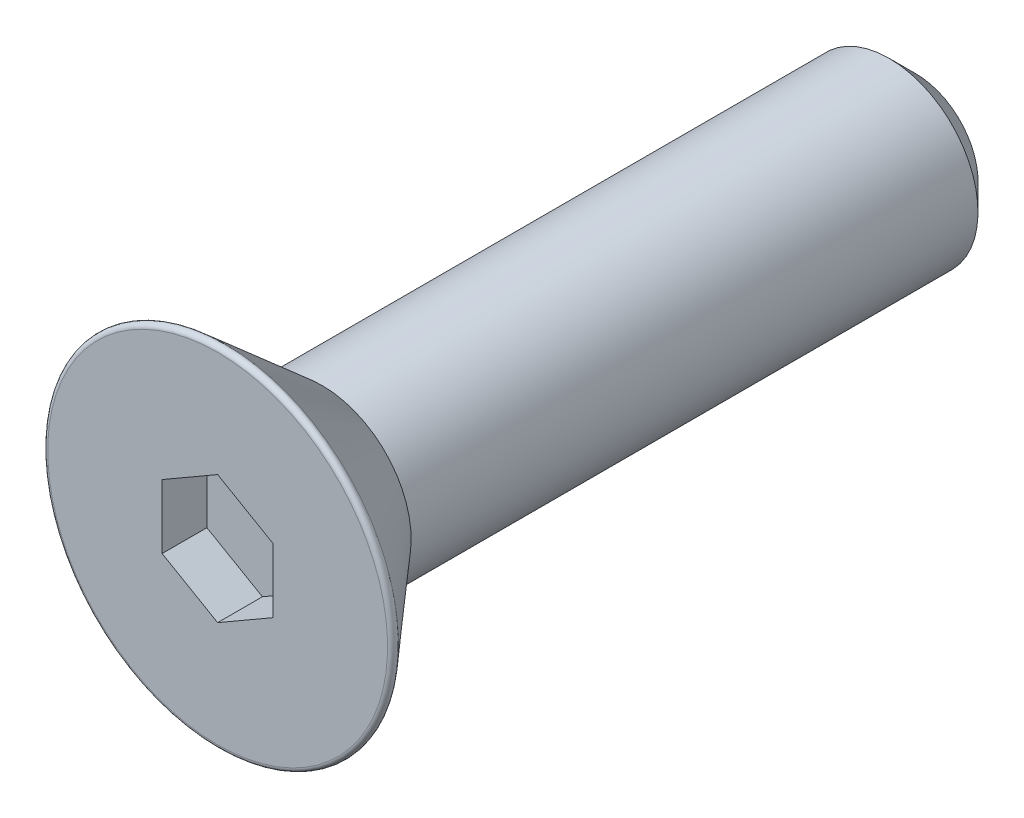
SolidWorks part; units mm, degrees
material "Alloy Steel"
ref_plane "Front Plane" through (0, 0, 0) normal (0, 0, 1) x (1, 0, 0)
ref_plane "Top Plane" through (0, 0, 0) normal (0, 1, 0) x (1, 0, 0)
ref_plane "Right Plane" through (0, 0, 0) normal (1, 0, 0) x (0, 0, -1)
sketch "Sketch1" plane through (0, 0, 0) normal (1, 0, 0) x (0, 0, -1)
  line L0 (-12.7, 0) -> (12.7, 0) construction
  line L1 (-12.7, 0) -> (-12.7, 6.7437)
  line L2 (-12.7, 6.7437) -> (-12.6182, 6.7437)
  line L3 (-12.6182, 6.7437) -> (-8.6106, 3.2599)
  line L4 (-12.6182, -6.7437) -> (-8.6106, -3.2599)
  line L5 (12.7, 0) -> (12.7, 3.175)
  line L6 (12.7, 3.175) -> (-8.6106, 3.175)
  line L7 (11.7475, 3.175) -> (12.7, 2.2225)
  line L8 (12.6206, 3.3125) -> (13.2556, 2.2126) construction
  line L9 (13.2556, 2.2126) -> (13.8906, 3.3125) construction
  line L10 (13.8906, 3.3125) -> (12.6206, 3.3125) construction
  line L11 (12.6603, 3.2437) -> (13.8509, 3.2437)
  line L12 (13.8509, 3.2437) -> (13.335, 2.3501)
  line L13 (13.335, 2.3501) -> (13.1762, 2.3501)
  line L14 (13.1762, 2.3501) -> (12.6603, 3.2437)
  line L15 (13.2556, 2.3501) -> (13.2556, 2.2126) construction
  line L16 (12.7, 3.175) -> (13.8112, 3.175) construction
  line L17 (13.2556, 3.3125) -> (13.2556, 3.175) construction
  line L18 (12.7, -3.175) -> (-8.6106, -3.175)
  arc A0 (-8.6106, 3.2599) -> (-8.3834, 3.175) centre (-8.3834, 3.5213) ccw
  point P2 (0, 0)
  point P23 (-10.6553, 0)
  point P27 (13.2556, 3.2437)
  point P30 (10.795, -3.175)
  point P31 (-8.6106, 6.7437)
  point P34 (-12.6182, -6.7437)
  dimension "Length" = 25.4
  dimension "Head Height" = 4.0894
  dimension "Head Diameter" = 13.4874
  dimension "Countersink Angle" = 82
  dimension "Screw Size Decimal Equivalent" = 6.35
  dimension "Pitch" = 1.27
  dimension "D4" = 0.1588
  dimension "D3" = 45
  dimension "D5" = 0.9525
  dimension "D6" = 2.0447
  dimension "D1" = 1.905
  dimension "D7" = 0.0818
sketch "Sketch8" plane through (0, 0, 0) normal (0, 0, 1) x (1, 0, 0)
  line L1 (0, 2.2914) -> (-1.9844, 1.1457)
  line L2 (-1.9844, 1.1457) -> (-1.9844, -1.1457)
  line L3 (-1.9844, -1.1457) -> (0, -2.2914)
  line L4 (0, -2.2914) -> (1.9844, -1.1457)
  line L5 (1.9844, -1.1457) -> (1.9844, 1.1457)
  line L6 (1.9844, 1.1457) -> (0, 2.2914)
  circle A0 centre (0, 0) radius 1.9844 construction
  dimension "Drive Size" = 3.9688
sketch "Sketch2" plane through (0, 0, 0) normal (1, 0, 0) x (0, 0, -1)
  line L0 (-12.6182, 6.7437) -> (-8.6106, 3.2599) construction
  line L1 (-12.7, 0) -> (-12.7, 6.7437) construction
  line L2 (-12.6182, 6.7437) -> (-8.5129, 3.175)
  line L3 (-12.7, 0) -> (-12.7, 6.7437)
  line L4 (-12.7, 6.7437) -> (-12.6182, 6.7437) construction
  line L5 (-12.7, 6.7437) -> (-12.6182, 6.7437)
  line L6 (-8.5129, 3.175) -> (11.7475, 3.175)
  line L7 (11.7475, 3.175) -> (12.7, 2.2225)
  line L8 (12.7, 2.2225) -> (12.7, 0)
  line L9 (12.7, 0) -> (-12.7, 0)
revolve "Revolve1" add sketch "Sketch2" angle 360 about L9
sketch "Sketch9" plane through (0, 0, 12.7) normal (0, 0, 1) x (1, 0, 0)
  line L0 (1.9844, -1.1457) -> (1.9844, 1.1457) construction
  line L1 (0, -2.2914) -> (1.9844, -1.1457) construction
  line L2 (-1.9844, -1.1457) -> (0, -2.2914) construction
  line L3 (-1.9844, 1.1457) -> (-1.9844, -1.1457) construction
  line L4 (0, 2.2914) -> (-1.9844, 1.1457) construction
  line L5 (1.9844, 1.1457) -> (0, 2.2914) construction
  line L6 (1.9844, -1.1457) -> (1.9844, 1.1457)
  line L7 (0, -2.2914) -> (1.9844, -1.1457)
  line L8 (-1.9844, -1.1457) -> (0, -2.2914)
  line L9 (-1.9844, 1.1457) -> (-1.9844, -1.1457)
  line L10 (0, 2.2914) -> (-1.9844, 1.1457)
  line L11 (1.9844, 1.1457) -> (0, 2.2914)
sketch "Sketch10" plane through (0, 0, 12.7) normal (0, 0, 1) x (1, 0, 0)
  circle A0 centre (0, 0) radius 2.2914
extrude "Cut-Extrude2" cut sketch "Sketch10" against normal up to vertex (2.0447 mm away) draft 45 up to point (0, 0, 10.6553)
extrude "Cut-Extrude1" cut sketch "Sketch9" against normal up to vertex (2.0447 mm away) up to point (0, 0, 10.6553)
ref_plane "Plane1" through (0, 0, 8.5129) normal (0, 0, 1) x (1, 0, 0)
split "Split1" trim tools "Plane1" bodies to split 111 resulting bodies 105 106
sketch "Sketch3" [suppressed] plane through (0, 0, -12.7) normal (0, 0, -1) x (-1, 0, 0)
  circle A0 centre (0, 0) radius 3.175 construction
  circle A1 centre (0, 0) radius 3.175
curve "Helix/Spiral1" [suppressed] pitch 1.27 height 25.4 turns 20
sketch "Sketch4" [suppressed] plane through (0, 0, 0) normal (1, 0, 0) x (0, 0, -1)
  line L0 (12.6603, 3.2437) -> (13.8509, 3.2437) construction
  line L1 (13.1762, 2.3501) -> (12.6603, 3.2437) construction
  line L2 (13.335, 2.3501) -> (13.1762, 2.3501) construction
  line L3 (13.8509, 3.2437) -> (13.335, 2.3501) construction
  line L4 (12.6603, 3.2437) -> (13.8509, 3.2437)
  line L5 (13.1762, 2.3501) -> (12.6603, 3.2437)
  line L6 (13.335, 2.3501) -> (13.1762, 2.3501)
  line L7 (13.8509, 3.2437) -> (13.335, 2.3501)
sweep "Cut-Sweep1" [suppressed] cut profiles "Sketch4" path "Helix/Spiral1"
sketch "Sketch7" plane through (0, 0, 8.5129) normal (0, 0, 1) x (1, 0, 0)
  circle A0 centre (0, 0) radius 3.175
extrude "Boss-Extrude2" add sketch "Sketch7" against normal up to next (21.2129 mm away) draft 20
sketch "Sketch12" plane through (0, 0, 0) normal (1, 0, 0) x (0, 0, -1)
  line L0 (-12.7, 0) -> (-12.7, 6.8148)
  line L1 (-12.7, 6.7437) -> (-12.7, -6.7437) construction
  line L2 (-12.7, 6.8148) -> (-11.9883, 6.1961)
  line L3 (-8.5129, 3.175) -> (-12.6182, 6.7437) construction
  line L4 (-12.0942, 6.2357) -> (-13.2564, 6.2357) construction
  line L5 (0, 0) -> (-12.2555, 0) construction
  line L6 (-12.2555, 6.0744) -> (-12.2555, 0)
  line L7 (-12.2555, 0) -> (-12.7, 0)
  arc A0 (-11.9883, 6.1961) -> (-12.2555, 6.0744) centre (-12.0942, 6.0744) ccw
  dimension "D1" = 6.2357
  dimension "D2" = 0.4445
revolve "Cut-Revolve1" cut sketch "Sketch12" angle 360 about L5
equation "\"D4@Sketch1\" = \"Pitch@Sketch1\" / 8"
equation "\"D5@Sketch1\"=\"Pitch@Sketch1\"*0.75"
equation "\"D4@Helix/Spiral1\"=\"Pitch@Sketch1\""
equation "\"D3@Helix/Spiral1\"=\"Length@Sketch1\""
equation "\"D6@Sketch1\"=\"Head Height@Sketch1\"/2"
equation "\"D1@Sketch1\"=\"Pitch@Sketch1\"*1.5"
equation "\"D7@Sketch1\"=\"Head Height@Sketch1\"*0.02"
equation "\"D1@Sketch12\"=0.4910in/2"
